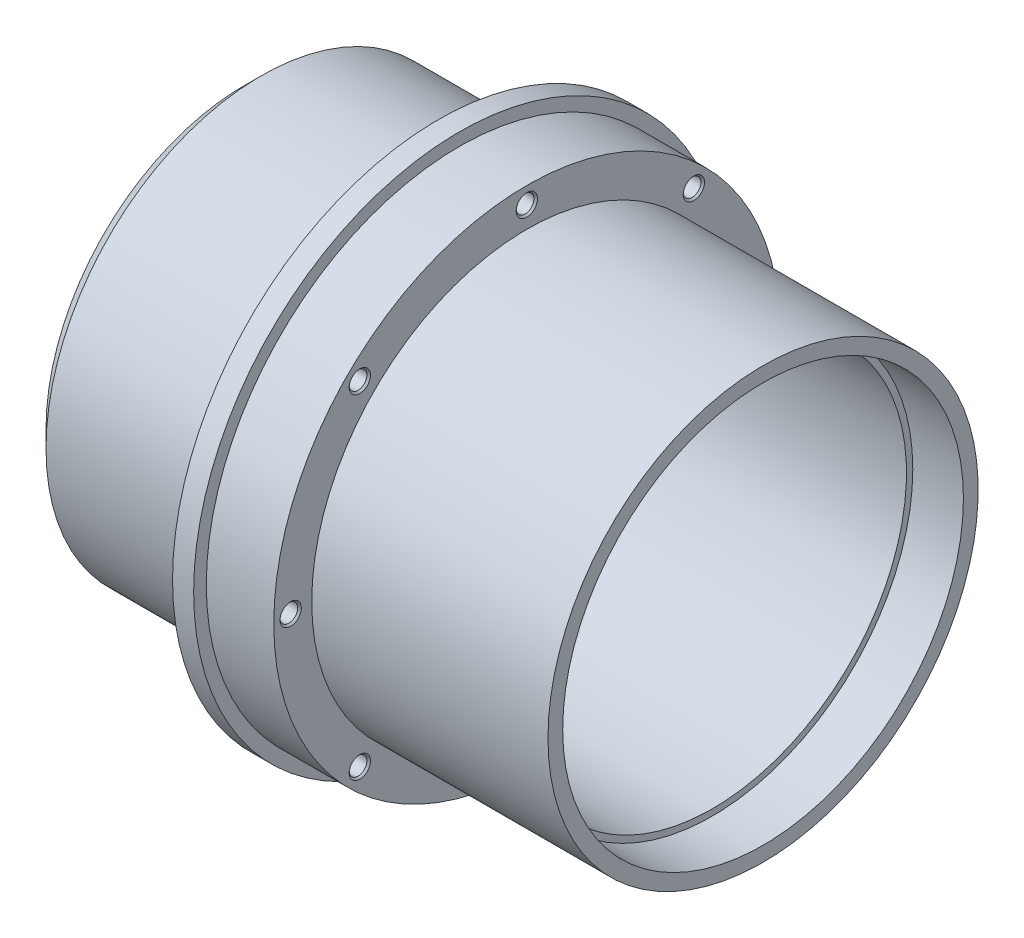
SolidWorks part; units mm, degrees
material "Stop 1060"
ref_plane "Płaszczyzna przednia" through (0, 0, 0) normal (0, 0, 1) x (1, 0, 0)
ref_plane "Płaszczyzna górna" through (0, 0, 0) normal (0, 1, 0) x (1, 0, 0)
ref_plane "Płaszczyzna prawa" through (0, 0, 0) normal (1, 0, 0) x (0, 0, -1)
sketch "Szkic1" plane through (0, 0, 0) normal (0, 0, 1) x (1, 0, 0)
  line L0 (0, 0) -> (77.4315, 0) construction
  line L2 (12, 40) -> (12, 12.0108)
  line L3 (24.5, 42) -> (14, 42)
  line L4 (44, 51) -> (4, 51)
  line L5 (24.5, 45) -> (24.5, 42)
  line L6 (24.5, 45) -> (36.5, 45)
  line L7 (36.5, 45) -> (36.5, 46)
  line L8 (111, 46) -> (36.5, 46)
  line L9 (46, 63) -> (46, 53)
  line L10 (51, 63) -> (46, 63)
  line L11 (51, 60) -> (51, 63)
  line L12 (123, 51) -> (67, 51)
  line L13 (51, 60) -> (67, 60)
  line L14 (111, 47.5) -> (111, 46)
  line L15 (111, 47.5) -> (123, 47.5)
  line L16 (123, 47.5) -> (123, 51)
  line L17 (0, 12.0108) -> (0, 47)
  line L18 (0, 12.0108) -> (12, 12.0108)
  line L19 (67, 60) -> (67, 51)
  line L20 (12, 40) -> (14, 42)
  line L21 (44, 51) -> (46, 53)
  line L22 (4, 51) -> (0, 47)
revolve "Obrót1" add sketch "Szkic1" angle 360 about L0
hole_wizard "Otwór gwintowany M51" positions "Szkic2" profile "Szkic4" tap size "M5" standard "DIN" end condition through all
sketch "Szkic2" plane through (67, 0, 0) normal (1, 0, 0) x (0, 0, -1)
  point P0 (0, 56)
  point P10 (39.598, 39.598)
  point P11 (56, 0)
  point P12 (39.598, -39.598)
  point P13 (0, -56)
  point P14 (-39.598, -39.598)
  point P15 (-56, 0)
  point P16 (-39.598, 39.598)
  point P17 (0, 0)
  dimension "D1" = 56
  dimension "D2" = 8
sketch "Szkic4" plane through (67, 56, 0) normal (0, 1, 0) x (0, 0, -1)
  line L0 (0, 0) -> (0, 67)
  line L1 (0, 67) -> (2.1, 67)
  line L2 (2.1, 67) -> (2.1, 0.425)
  line L3 (2.1, 0.425) -> (2.525, 0)
  line L5 (2.525, 0) -> (0, 0)
  line L6 (-2.1, 0.425) -> (-2.525, 0) construction
  line L11 (0, -6.35) -> (0, 107.95) construction
  dimension "Średnica otworu gwintowanego na wylot" = 4.2
  dimension "Głębokość otworu gwintowanego na wylot" = 67
  dimension "Średnica zewnętrznego pogłębienia stożkowego" = 5.05
  dimension "Kąt zewnętrznego pogłębienia stożkowego" = 90
cosmetic thread "Gwint otworu1"
cosmetic thread "Gwint otworu2"
cosmetic thread "Gwint otworu3"
cosmetic thread "Gwint otworu4"
cosmetic thread "Gwint otworu5"
cosmetic thread "Gwint otworu6"
cosmetic thread "Gwint otworu7"
cosmetic thread "Gwint otworu8"
